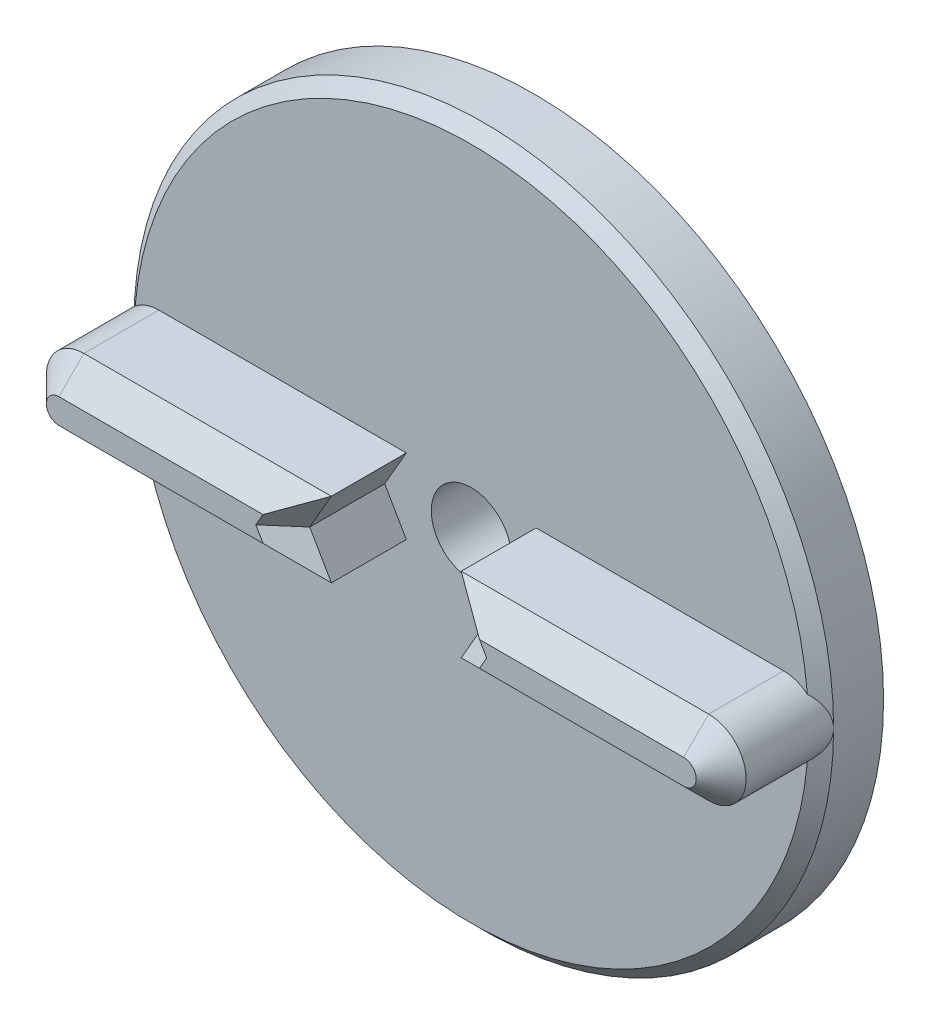
SolidWorks part; units mm, degrees
ref_plane "正面" through (0, 0, 0) normal (0, 0, 1) x (1, 0, 0)
ref_plane "平面" through (0, 0, 0) normal (0, 1, 0) x (1, 0, 0)
ref_plane "右側面" through (0, 0, 0) normal (1, 0, 0) x (0, 0, -1)
sketch "ｽｹｯﾁ1" plane through (0, 0, 0) normal (0, 0, 1) x (1, 0, 0)
  circle A0 centre (0, 0) radius 14
  dimension "D1" = 28
extrude "ﾎﾞｽ - 押し出し1" add sketch "ｽｹｯﾁ1" along normal blind 2.5
sketch "ｽｹｯﾁ2" plane through (0, 0, 2.5) normal (0, 0, 1) x (1, 0, 0)
  line L0 (-12.5, 0) -> (12.5, 0) construction
  line L1 (-12.5, 1.5) -> (12.5, 1.5)
  line L2 (-12.5, -1.5) -> (12.5, -1.5)
  arc A0 (-12.5, 1.5) -> (-12.5, -1.5) centre (-12.5, 0) ccw
  arc A1 (12.5, -1.5) -> (12.5, 1.5) centre (12.5, 0) ccw
  circle A2 centre (0, 0) radius 14 construction
  point P2 (0, 0)
  dimension "D1" = 3
extrude "ﾎﾞｽ - 押し出し2" add sketch "ｽｹｯﾁ2" along normal blind 4
chamfer "面取り1" distance 0.5 angle 45 2 edges at (0, 14, 2.5) (0, -14, 2.5)
sketch "ｽｹｯﾁ5" plane through (0, 0, 0) normal (0, 0, -1) x (-1, 0, 0)
  line L1 (-4.4, 1.4) -> (4.4, 1.4)
  line L2 (-4.4, 1.4) -> (-4.4, -1.4)
  line L3 (-4.4, -1.4) -> (4.4, -1.4)
  line L4 (4.4, 1.4) -> (4.4, -1.4)
  line L5 (-4.4, 1.4) -> (4.4, -1.4) construction
  line L6 (-4.4, -1.4) -> (4.4, 1.4) construction
  point P0 (0, 0)
  dimension "D1" = 2.8
  dimension "D2" = 8.8
extrude "ﾎﾞｽ - 押し出し3" add sketch "ｽｹｯﾁ5" along normal blind 2
sketch "ｽｹｯﾁ3" plane through (0, 0, 0) normal (0, 0, -1) x (-1, 0, 0)
  circle A0 centre (0, 0) radius 1.6
  dimension "D1" = 3.2
extrude "ｶｯﾄ - 押し出し4" cut sketch "ｽｹｯﾁ3" against normal through all and the other way blind 2.5
sketch "ｽｹｯﾁ6" plane through (0, 0, 6.5) normal (0, 0, 1) x (1, 0, 0)
  line L1 (3.4641, 0) -> (1.7321, 3)
  line L2 (1.7321, 3) -> (-1.7321, 3)
  line L3 (-1.7321, 3) -> (-3.4641, 0)
  line L4 (-3.4641, 0) -> (-1.7321, -3)
  line L5 (-1.7321, -3) -> (1.7321, -3)
  line L6 (1.7321, -3) -> (3.4641, 0)
  circle A0 centre (0, 0) radius 3 construction
  dimension "D1" = 6
extrude "ｶｯﾄ - 押し出し5" cut sketch "ｽｹｯﾁ6" against normal up to surface (4 mm away) up to face at (0, 3.4876, 2.5)
chamfer "面取り2" distance 1 angle 45 10 edges at (3.0311, 0.75, 6.5) (7.549, 1.5, 6.5) (14, 0, 6.5) (7.549, -1.5, 6.5) (3.0311, -0.75, 6.5) (-7.549, -1.5, 6.5) (-14, 0, 6.5) (-7.549, 1.5, 6.5) (-3.0311, 0.75, 6.5) (-3.0311, -0.75, 6.5)
